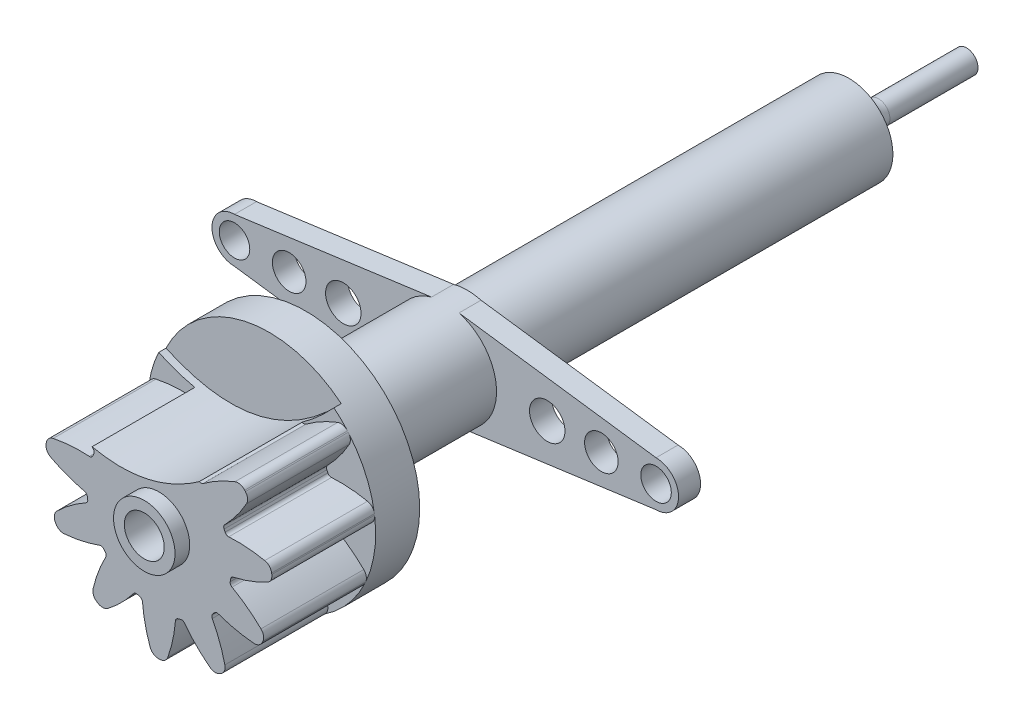
SolidWorks part; units mm, degrees
note: The reader was unsure of these and kept them because the rebuilt part matched: shared geometry of "Esquisse2<3>".
ref_plane "Plan de face" through (0, 0, 0) normal (0, 0, 1) x (1, 0, 0)
ref_plane "Plan de dessus" through (0, 0, 0) normal (0, 1, 0) x (1, 0, 0)
ref_plane "Plan de droite" through (0, 0, 0) normal (1, 0, 0) x (0, 0, -1)
sketch "Esquisse1" plane through (0, 0, 0) normal (0, 0, 1) x (1, 0, 0)
  circle A0 centre (0, 0) radius 0.5968
extrude "Boss.-Extru.1" add sketch "Esquisse1" along normal blind 6.8
sketch "Esquisse2" plane through (0, 0, 6.8) normal (0, 0, 1) x (1, 0, 0)
  line L0 (2.871, 0.3068) -> (0.187, 0.6728)
  line L1 (2.871, -0.3068) -> (0.187, -0.6728)
  line L2 (0, 0) -> (0, -1.5357) construction
  line L3 (-2.871, 0.3068) -> (-0.187, 0.6728)
  line L4 (-2.871, -0.3068) -> (-0.187, -0.6728)
  circle A0 centre (0, 0) radius 0.6984
  arc A1 (2.871, -0.3068) -> (2.871, 0.3068) centre (2.871, 0) ccw
  circle A2 centre (2.871, 0) radius 0.208
  circle A3 centre (2.1263, 0) radius 0.2286
  circle A4 centre (1.389, 0) radius 0.2416
  circle A5 centre (0, 0) radius 0.5968
  circle A6 centre (-1.389, 0) radius 0.2416
  circle A7 centre (-2.1263, 0) radius 0.2286
  circle A8 centre (-2.871, 0) radius 0.208
  arc A9 (-2.871, -0.3068) -> (-2.871, 0.3068) centre (-2.871, 0) cw
extrude "Boss.-Extru.2" add sketch "Esquisse2" along normal blind 0.3 separate body contours A9 L4 A0 L3 A7 A6 A8 | L1 A1 L0 A0 A4 A3 A2
extrude "Boss.-Extru.3" add sketch "Esquisse2<3>" along normal blind 0.6
sketch "Esquisse2<3>" plane through (0, 0, 6.8) normal (0, 0, 1) x (1, 0, 0) same geometry as "Esquisse2"
sketch "Esquisse3" plane through (0, 0, 7.4) normal (0, 0, 1) x (1, 0, 0)
  circle A0 centre (0, 0) radius 1.5522
  circle A1 centre (0, 0) radius 0.2718
extrude "Boss.-Extru.4" add sketch "Esquisse3" along normal blind 3.6
sketch "Esquisse4" plane through (0, 0, 11) normal (0, 0, 1) x (1, 0, 0)
  line L0 (0, 0.9829) -> (0, 2.0041) construction
  arc A0 (0.0165, 0.9827) -> (-0.0165, 0.9827) centre (0, 0) ccw
  arc A1 (-0.0641, 1.0149) -> (-0.0165, 0.9827) centre (-0.0174, 1.0327) ccw
  arc A3 (0.2996, 1.4472) -> (0.0641, 1.0149) centre (1.7935, 0.353) ccw
  arc A4 (-0.2996, 1.4472) -> (-0.0641, 1.0149) centre (-1.7935, 0.353) cw
  arc A5 (0.0165, 0.9827) -> (0.0641, 1.0149) centre (0.0174, 1.0327) ccw
  arc A6 (0.4296, 1.4916) -> (0.2996, 1.4472) centre (0.3964, 1.3762) ccw
  arc A7 (-0.2996, 1.4472) -> (-0.4296, 1.4916) centre (-0.3964, 1.3762) ccw
  arc A8 (0.4296, 1.4916) -> (-0.4296, 1.4916) centre (0, 0) ccw
  point P9 (-0.0517, 0.9815)
  point P15 (0.0517, 0.9815)
  dimension "D1" = 0.05
  dimension "D2" = 0.12
extrude "Enlèv. mat.-Extru.2" cut sketch "Esquisse4" against normal blind 1.4
pattern_circular "Répétition circulaire1" count 11 over 360 about axis through (0, 0, 0) along (0, 0, 1) of "Enlèv. mat.-Extru.2"
sketch "Esquisse5" plane through (0, 0, 11) normal (0, 0, 1) x (1, 0, 0)
  circle A0 centre (0, 0) radius 0.2718
  circle A1 centre (0, 0) radius 0.4188
extrude "Boss.-Extru.5" add sketch "Esquisse5" along normal blind 0.2
sketch "Esquisse8" plane through (0, 0, 11) normal (0, 0, 1) x (1, 0, 0)
  arc A0 (1.0988, 1.3314) -> (-1.5599, 0.7393) centre (0, 0) ccw
  spline S0 degree 3 poles (-1.5599, 0.7393) (-1.1942, 0.5454) (-0.2409, 0.2861) (0.6062, 0.75) (1.0988, 1.3314) knots 0.031578 0.031578 0.031578 0.031578 0.351065 0.898413 0.898413 0.898413 0.898413
extrude "Enlèv. mat.-Extru.4" cut sketch "Esquisse8" against normal blind 1.5
sketch "Esquisse9" plane through (0, 0, 7.4) normal (0, 0, -1) x (-1, 0, 0)
  circle A0 centre (0, 0) radius 1.5522
  circle A2 centre (0, 0) radius 0.6984
extrude "Enlèv. mat.-Extru.5" cut sketch "Esquisse9" against normal blind 1.6
sketch "Esquisse10" plane through (0, 0, 0) normal (0, 0, -1) x (-1, 0, 0)
  circle A0 centre (0, 0) radius 0.1568
  circle A1 centre (0, 0) radius 0.7175
extrude "Enlèv. mat.-Extru.6" cut sketch "Esquisse10" against normal blind 1.6
fillet "Congé1" radius 0.4 1 edges at (-0.1568, 0, 1.6)
